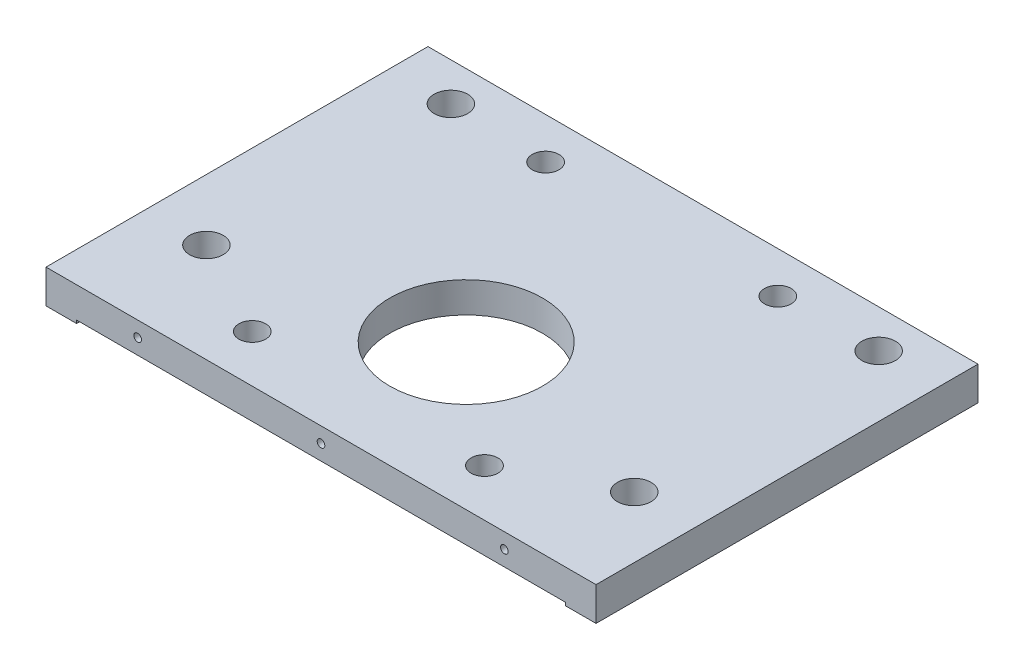
SolidWorks part; units mm, degrees
ref_plane "前视基准面" through (0, 0, 0) normal (0, 0, 1) x (1, 0, 0)
ref_plane "上视基准面" through (0, 0, 0) normal (0, 1, 0) x (1, 0, 0)
ref_plane "右视基准面" through (0, 0, 0) normal (1, 0, 0) x (0, 0, -1)
sketch "草图1" plane through (0, 0, 0) normal (0, 1, 0) x (1, 0, 0)
  line L1 (180, -125) -> (-180, -125)
  line L2 (180, -125) -> (180, 125)
  line L3 (180, 125) -> (-180, 125)
  line L4 (-180, -125) -> (-180, 125)
  line L5 (180, -125) -> (-180, 125) construction
  line L6 (180, 125) -> (-180, -125) construction
  point P0 (0, 0)
  dimension "D1" = 360
  dimension "D2" = 250
extrude "凸台-拉伸1" add sketch "草图1" along normal blind 22
sketch "草图2" plane through (0, 0, 0) normal (0, -1, 0) x (1, 0, 0)
  line L0 (0, 0) -> (0, 137.7755) construction
  line L1 (0, 0) -> (196.5572, 0) construction
  circle A0 centre (0, 30) radius 50
  circle A1 centre (-140, 60) radius 11
  point P4 (0, 0)
  dimension "D3" = 22
  dimension "D5" = 100
  dimension "D1" = 280
  dimension "D2" = 60
  dimension "D4" = 30
extrude "切除-拉伸1" cut sketch "草图2" against normal up to next
sketch "草图3" plane through (0, 0, 0) normal (0, -1, 0) x (1, 0, 0)
  line L0 (-160, 125) -> (-160, -125)
  line L1 (-180, 125) -> (180, 125) construction
  line L2 (180, -125) -> (-180, -125) construction
  line L3 (-160, -125) -> (160, -125)
  line L4 (160, -125) -> (160, 125)
  line L5 (160, 125) -> (-160, 125)
  line L6 (0, 0) -> (0, 66.5699) construction
  dimension "D1" = 320
extrude "切除-拉伸2" cut sketch "草图3" against normal blind 2
pattern_linear "阵列(线性)1" count 2 spacing 280 along (1, 0, 0) count 2 spacing 160 along (0, 0, -1) of face at (-140, 22, 71)
hole_wizard "M20 螺纹孔1" positions "草图4" profile "草图5" tap size "M20" standard "GB" end condition through all
sketch "草图4" plane through (0, 2, 0) normal (0, -1, 0) x (-1, 0, 0)
  line L0 (0, 0) -> (0, -99.2058) construction
  line L2 (0, 0) -> (93.4574, 0) construction
  point P0 (76, -94)
  dimension "D1" = 152
  dimension "D2" = 94
sketch "草图5" plane through (-76, 2, 94) normal (1, 0, 0) x (0, 0, -1)
  line L0 (0, 0) -> (0, 20)
  line L1 (0, 20) -> (8.75, 20)
  line L2 (8.75, 20) -> (8.75, 0)
  line L5 (8.75, 0) -> (0, 0)
  line L11 (0, -6.35) -> (0, 107.95) construction
  dimension "通孔螺纹孔钻头直径" = 17.5
  dimension "通孔螺纹孔钻头深度" = 20
cosmetic thread "孔螺蚊线1" parameters "D2"=20
pattern_linear "阵列(线性)2" count 2 spacing 192 along (0, 0, -1) count 2 spacing 152 along (1, 0, 0) of "M20 螺纹孔1"
hole_wizard "M6 螺纹孔1" positions "草图6" profile "草图7" tap size "M6" standard "GB"
sketch "草图6" plane through (0, 0, -125) normal (0, 0, -1) x (-1, 0, 0)
  line L0 (-180, 22) -> (180, 22) construction
  line L2 (0, 0) -> (0, -26.3902) construction
  point P0 (-120, 12)
  point P2 (0, 12)
  point P4 (120, 12)
  point P15 (0, 0)
  point P16 (0, 0)
  point P17 (0, 0)
  dimension "D1" = 10
  dimension "D2" = 120
  dimension "D3" = 120
cosmetic thread "孔螺蚊线2" parameters "D2"=6
cosmetic thread "孔螺蚊线3" parameters "D2"=6
cosmetic thread "孔螺蚊线4" parameters "D2"=6
sketch "草图7" plane through (120, 12, -125) normal (1, 0, 0) x (0, 1, 0)
  line L0 (0, 0) -> (0, 16.5022)
  line L1 (0, 16.5022) -> (2.5, 15)
  line L2 (2.5, 15) -> (2.5, 0)
  line L5 (2.5, 0) -> (0, 0)
  line L10 (0, 16.5022) -> (-2.5, 15) construction
  line L11 (0, -6.35) -> (0, 107.95) construction
  dimension "螺纹孔钻头直径" = 5
  dimension "螺纹孔钻头深度" = 15
  dimension "导头角度" = 118
mirror "镜向1" about plane through (0, 0, 0) normal (0, 0, 1) of "M6 螺纹孔1"
